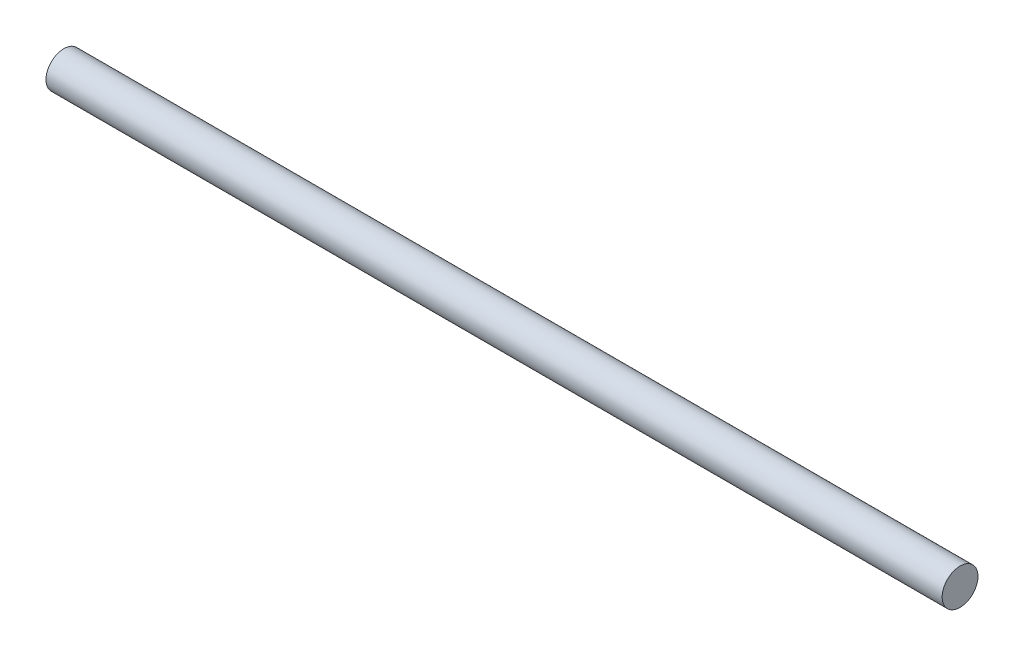
SolidWorks part; units mm, degrees
ref_plane "Front Plane" through (0, 0, 0) normal (0, 0, 1) x (1, 0, 0)
ref_plane "Top Plane" through (0, 0, 0) normal (0, 1, 0) x (1, 0, 0)
ref_plane "Right Plane" through (0, 0, 0) normal (1, 0, 0) x (0, 0, -1)
sketch "Croquis1" plane through (0, 0, 0) normal (1, 0, 0) x (0, 0, -1)
  circle A0 centre (0, 0) radius 4
  dimension "D1" = 8
extrude "Saliente-Extruir1" add sketch "Croquis1" along normal blind 200
ref_axis "Eje1" through (200, 0, 0) along (-1, 0, 0)
